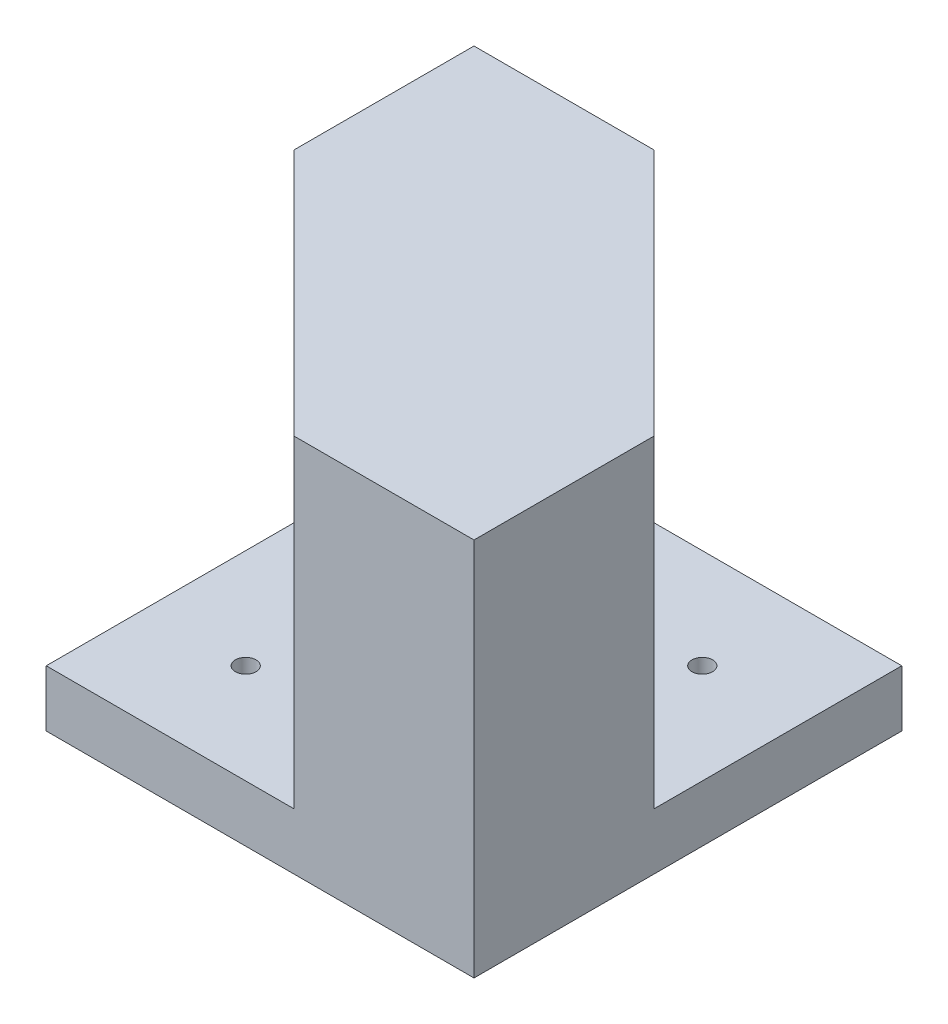
SolidWorks part; units mm, degrees
ref_plane "Front Plane" through (0, 0, 0) normal (0, 0, 1) x (1, 0, 0)
ref_plane "Top Plane" through (0, 0, 0) normal (0, 1, 0) x (1, 0, 0)
ref_plane "Right Plane" through (0, 0, 0) normal (1, 0, 0) x (0, 0, -1)
sketch "Sketch1" plane through (0, 0, 0) normal (0, 1, 0) x (1, 0, 0)
  line L1 (-33.655, 33.655) -> (33.655, 33.655)
  line L2 (-33.655, 33.655) -> (-33.655, -33.655)
  line L3 (-33.655, -33.655) -> (33.655, -33.655)
  line L4 (33.655, 33.655) -> (33.655, -33.655)
  line L5 (-33.655, 33.655) -> (33.655, -33.655) construction
  line L6 (-33.655, -33.655) -> (33.655, 33.655) construction
  circle A0 centre (17.9605, 17.9605) radius 1.625
  circle A2 centre (-17.9605, -17.9605) radius 1.625
  circle A4 centre (-17.9605, 17.9605) radius 1.625 [skipped]
  circle A5 centre (17.9605, -17.9605) radius 1.625 [skipped]
  point P0 (0, 0)
  point P20 (0, 0)
  dimension "D1" = 3.25
  dimension "D2" = 25.4
  dimension "D4" = 67.31
  dimension "D3" = 4
extrude "Boss-Extrude1" add sketch "Sketch1" along normal blind 8.89
sketch "Sketch2" plane through (0, 8.89, 0) normal (0, 1, 0) x (1, 0, 0)
  line L0 (-17.9431, 33.655) -> (33.655, -17.9431)
  line L1 (33.655, -17.9431) -> (33.655, -5.3707)
  line L2 (33.655, -5.3707) -> (-5.3707, 33.655)
  line L3 (-5.3707, 33.655) -> (-17.9431, 33.655)
  line L6 (17.9431, -33.655) -> (-33.655, 17.9431)
  line L8 (33.655, -33.655) -> (33.655, 33.655) construction
  line L9 (33.655, 33.655) -> (-33.655, 33.655) construction
  line L10 (-33.655, -33.655) -> (33.655, -33.655) construction
  line L11 (-33.655, 33.655) -> (-33.655, -33.655) construction
  line L12 (-33.655, 17.9431) -> (-33.655, 5.3707)
  line L13 (-33.655, 5.3707) -> (5.3707, -33.655)
  line L14 (5.3707, -33.655) -> (17.9431, -33.655)
  line L15 (-33.655, 17.9431) -> (-33.655, 33.655)
  line L16 (-33.655, 33.655) -> (-17.9431, 33.655)
  line L17 (17.9431, -33.655) -> (33.655, -33.655)
  line L18 (33.655, -33.655) -> (33.655, -17.9431)
  line M14 (33.655, -33.655) -> (33.655, 33.655)
  line M15 (33.655, 33.655) -> (-33.655, 33.655)
  line M16 (-33.655, 33.655) -> (-33.655, -33.655)
  line M17 (-33.655, -33.655) -> (33.655, -33.655)
  dimension "D1" = 45
  dimension "D2" = 8.89
  dimension "D3" = 8.89
  dimension "D4" = 40
extrude "Boss-Extrude2" add sketch "Sketch2" along normal blind 50.8 contours L13 L6 M16 M17 | L6 L0 M17 M14 M15 M16 | L2 L0 M14 M15 region at (10.8537, 8.89, -10.8537) region at (0, 8.89, 0) region at (-10.8537, 8.89, 10.8537)
sketch "Sketch3" plane through (-14.1421, 0, 14.1421) normal (-0.7071, 0, 0.7071) x (0.7071, 0, 0.7071)
  line L0 (-17.9605, 52.2505) -> (17.9605, 16.3295) construction
  line L1 (0, 8.89) -> (27.5954, 8.89) construction
  line L2 (0, 0) -> (0, 34.29) construction
  line L3 (0, 34.29) -> (-27.5954, 34.29) construction
  line L4 (-27.5954, 59.69) -> (-27.5954, 8.89) construction
  circle A0 centre (-17.9605, 52.2505) radius 2
  circle A1 centre (17.9605, 16.3295) radius 2
  circle A2 centre (0, 34.29) radius 2
  circle A3 centre (17.9605, 52.2505) radius 2
  circle A4 centre (-17.9605, 16.3295) radius 2
  point P17 (-17.9605, 16.3295)
  dimension "4mm" = 4
  dimension "D2" = 45
  dimension "D3" = 50.8
extrude "Cut-Extrude2" cut sketch "Sketch3" against normal blind 127
